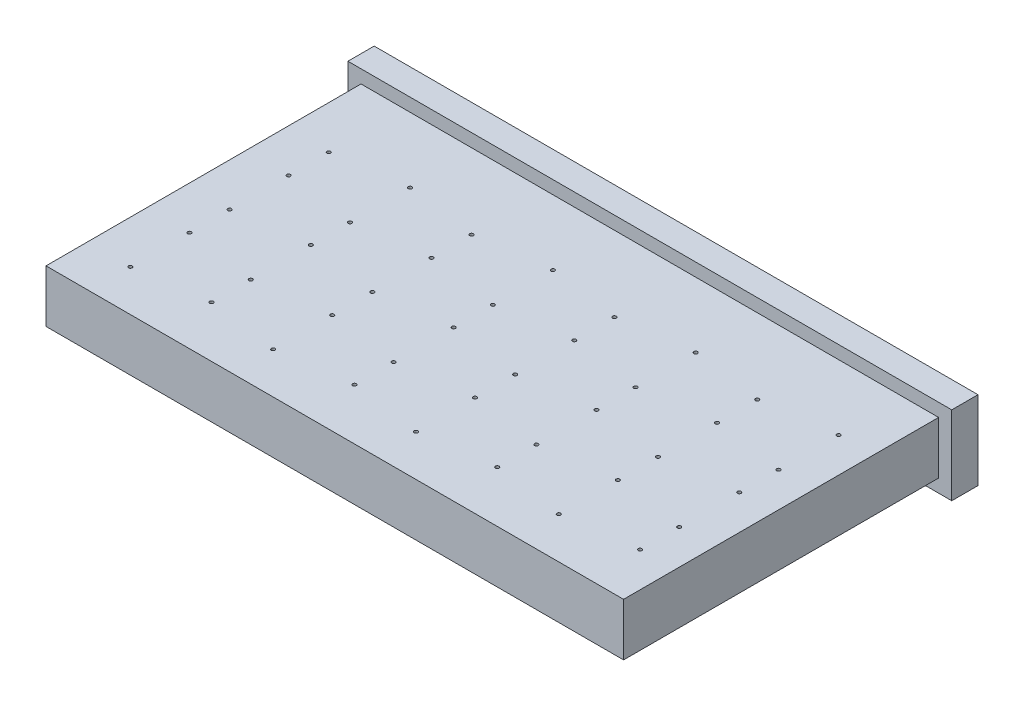
SolidWorks part; units mm, degrees
material "ABS"
ref_plane "X-Y Datum" through (0, 0, 0) normal (0, 0, 1) x (1, 0, 0)
ref_plane "X-Z Datum" through (0, 0, 0) normal (0, 1, 0) x (1, 0, 0)
ref_plane "Y-Z Datum" through (0, 0, 0) normal (1, 0, 0) x (0, 0, -1)
sketch "Sketch1" plane through (0, 0, 0) normal (0, 0, 1) x (1, 0, 0)
  line L1 (-146.05, -19.05) -> (146.05, -19.05)
  line L2 (-146.05, -19.05) -> (-146.05, 19.05)
  line L3 (-146.05, 19.05) -> (146.05, 19.05)
  line L4 (146.05, -19.05) -> (146.05, 19.05)
  line L5 (-146.05, -19.05) -> (146.05, 19.05) construction
  line L6 (-146.05, 19.05) -> (146.05, -19.05) construction
  point P0 (0, 0)
  dimension "D1" = 38.1
  dimension "D2" = 292.1
extrude "Boss-Extrude1" add sketch "Sketch1" along normal blind 12.7
sketch "Sketch2" plane through (0, 0, 12.7) normal (0, 0, 1) x (1, 0, 0)
  line L0 (-146.05, 0) -> (146.05, 0) construction
  line L1 (146.05, -19.05) -> (146.05, 19.05) construction
  line L3 (-139.7, -12.7) -> (139.7, -12.7)
  line L4 (-139.7, -12.7) -> (-139.7, 12.7)
  line L5 (-139.7, 12.7) -> (139.7, 12.7)
  line L6 (139.7, -12.7) -> (139.7, 12.7)
  line L7 (-139.7, -12.7) -> (139.7, 12.7) construction
  line L8 (-139.7, 12.7) -> (139.7, -12.7) construction
  point P0 (0, 0)
  point P6 (0, 0)
  dimension "D2" = 279.4
  dimension "D1" = 25.4
extrude "Boss-Extrude2" add sketch "Sketch2" along normal blind 152.4
sketch "Sketch3" plane through (0, 12.7, 0) normal (0, 1, 0) x (1, 0, 0)
  line L0 (139.7, -88.9) -> (-139.7, -88.9) construction
  line L1 (139.7, -165.1) -> (139.7, -12.7) construction
  line L2 (-139.7, -165.1) -> (-139.7, -12.7) construction
  line L4 (139.7, -19.05) -> (-139.7, -19.05)
  line L5 (139.7, -19.05) -> (139.7, -158.75)
  line L6 (139.7, -158.75) -> (-139.7, -158.75)
  line L7 (-139.7, -19.05) -> (-139.7, -158.75)
  line L8 (139.7, -19.05) -> (-139.7, -158.75) construction
  line L9 (139.7, -158.75) -> (-139.7, -19.05) construction
  circle A0 centre (130.81, -149.86) radius 1.27
  point P6 (0, -88.9)
  dimension "D4" = 2.54
  dimension "D1" = 139.7
  dimension "D2" = 279.4
  dimension "D3" = 8.89
  dimension "D5" = 8.89
sketch "Sketch4" plane through (0, -12.7, 0) normal (0, -1, 0) x (1, 0, 0)
  circle A0 centre (-118.8948, 145.1079) radius 0.875 construction
  circle A1 centre (-118.8948, 145.1079) radius 0.875
  circle A2 centre (88.3692, 49.1061) radius 0.875 construction
  circle A3 centre (122.8692, 44.2911) radius 0.875 construction
  circle A4 centre (122.8692, 73.351) radius 0.875 construction
  circle A5 centre (88.3692, 68.5361) radius 0.875 construction
  circle A6 centre (88.3692, 97.107) radius 0.875 construction
  circle A7 centre (122.8692, 92.2921) radius 0.875 construction
  circle A8 centre (122.8692, 121.357) radius 0.875 construction
  circle A9 centre (122.8692, 140.293) radius 0.875 construction
  circle A10 centre (88.3692, 116.5421) radius 0.875 construction
  circle A11 centre (88.3692, 145.1079) radius 0.875 construction
  circle A12 centre (53.7812, 140.293) radius 0.875 construction
  circle A13 centre (53.7812, 121.357) radius 0.875 construction
  circle A14 centre (53.7812, 92.2921) radius 0.875 construction
  circle A15 centre (53.7812, 73.351) radius 0.875 construction
  circle A16 centre (53.7812, 44.2911) radius 0.875 construction
  circle A17 centre (19.2812, 68.5361) radius 0.875 construction
  circle A18 centre (19.2812, 97.107) radius 0.875 construction
  circle A19 centre (19.2812, 116.5421) radius 0.875 construction
  circle A20 centre (19.2812, 145.1079) radius 0.875 construction
  circle A21 centre (-15.3068, 140.293) radius 0.875 construction
  circle A22 centre (-15.3068, 92.2921) radius 0.875 construction
  circle A23 centre (-49.8068, 97.107) radius 0.875 construction
  circle A24 centre (19.2812, 49.1061) radius 0.875 construction
  circle A25 centre (-15.3068, 44.2911) radius 0.875 construction
  circle A26 centre (-15.3068, 73.351) radius 0.875 construction
  circle A27 centre (-49.8068, 68.5361) radius 0.875 construction
  circle A28 centre (-49.8068, 49.1061) radius 0.875 construction
  circle A29 centre (-49.8068, 116.5421) radius 0.875 construction
  circle A30 centre (-49.8068, 145.1079) radius 0.875 construction
  circle A31 centre (-84.3948, 121.357) radius 0.875 construction
  circle A32 centre (-84.3948, 92.2921) radius 0.875 construction
  circle A33 centre (-84.3948, 73.351) radius 0.875 construction
  circle A34 centre (-84.3948, 44.2911) radius 0.875 construction
  circle A35 centre (-118.8948, 49.1061) radius 0.875 construction
  circle A36 centre (-118.8948, 68.5361) radius 0.875 construction
  circle A37 centre (-118.8948, 97.107) radius 0.875 construction
  circle A38 centre (-118.8948, 116.5421) radius 0.875 construction
  circle A39 centre (-84.3948, 140.293) radius 0.875 construction
  circle A40 centre (88.3692, 49.1061) radius 0.875
  circle A41 centre (122.8692, 44.2911) radius 0.875
  circle A42 centre (122.8692, 73.351) radius 0.875
  circle A43 centre (88.3692, 68.5361) radius 0.875
  circle A44 centre (88.3692, 97.107) radius 0.875
  circle A45 centre (122.8692, 92.2921) radius 0.875
  circle A46 centre (122.8692, 121.357) radius 0.875
  circle A47 centre (122.8692, 140.293) radius 0.875
  circle A48 centre (88.3692, 116.5421) radius 0.875
  circle A49 centre (88.3692, 145.1079) radius 0.875
  circle A50 centre (53.7812, 140.293) radius 0.875
  circle A51 centre (53.7812, 121.357) radius 0.875
  circle A52 centre (53.7812, 92.2921) radius 0.875
  circle A53 centre (53.7812, 73.351) radius 0.875
  circle A54 centre (53.7812, 44.2911) radius 0.875
  circle A55 centre (19.2812, 68.5361) radius 0.875
  circle A56 centre (19.2812, 97.107) radius 0.875
  circle A57 centre (19.2812, 116.5421) radius 0.875
  circle A58 centre (19.2812, 145.1079) radius 0.875
  circle A59 centre (-15.3068, 140.293) radius 0.875
  circle A60 centre (-15.3068, 92.2921) radius 0.875
  circle A61 centre (-49.8068, 97.107) radius 0.875
  circle A62 centre (19.2812, 49.1061) radius 0.875
  circle A63 centre (-15.3068, 44.2911) radius 0.875
  circle A64 centre (-15.3068, 73.351) radius 0.875
  circle A65 centre (-49.8068, 68.5361) radius 0.875
  circle A66 centre (-49.8068, 49.1061) radius 0.875
  circle A67 centre (-49.8068, 116.5421) radius 0.875
  circle A68 centre (-49.8068, 145.1079) radius 0.875
  circle A69 centre (-118.8948, 145.1079) radius 0.875
  circle A70 centre (-84.3948, 121.357) radius 0.875
  circle A71 centre (-84.3948, 92.2921) radius 0.875
  circle A72 centre (-84.3948, 73.351) radius 0.875
  circle A73 centre (-84.3948, 44.2911) radius 0.875
  circle A74 centre (-118.8948, 49.1061) radius 0.875
  circle A75 centre (-118.8948, 68.5361) radius 0.875
  circle A76 centre (-118.8948, 97.107) radius 0.875
  circle A77 centre (-118.8948, 116.5421) radius 0.875
  circle A78 centre (-84.3948, 140.293) radius 0.875
  circle A79 centre (-15.3068, 121.357) radius 0.875 construction
  circle A80 centre (-15.3068, 121.357) radius 0.875
extrude "Cut-Extrude1" cut sketch "Sketch4" against normal through all contours A77 | A75 | A72 | A74 | A73 | A65 | A67 | A68 | A63 | A64 | A57 | A58 | A51 | A45 | A43 | A40 | A41 | A42 | A44 | A1 | A78 | A70 | A76 | A71 | A66 | A61 | A59 | A60 | A62 | A55 | A56 | A50 | A49 | A47 | A46 | A48 | A44 | A54 | A52 | A53 | A80 region at (-118.8948, -12.7, 145.1079) region at (88.3692, -12.7, 49.1061) region at (122.8692, -12.7, 44.2911) region at (122.8692, -12.7, 73.351) region at (88.3692, -12.7, 68.5361) region at (88.3692, -12.7, 97.107) region at (122.8692, -12.7, 92.2921) region at (53.7812, -12.7, 121.357) region at (19.2812, -12.7, 116.5421) region at (19.2812, -12.7, 145.1079) region at (-15.3068, -12.7, 44.2911) region at (-15.3068, -12.7, 73.351) region at (-49.8068, -12.7, 68.5361) region at (-49.8068, -12.7, 116.5421) region at (-49.8068, -12.7, 145.1079) region at (-84.3948, -12.7, 73.351) region at (-84.3948, -12.7, 44.2911) region at (-118.8948, -12.7, 49.1061) region at (-118.8948, -12.7, 68.5361) region at (-118.8948, -12.7, 116.5421)
